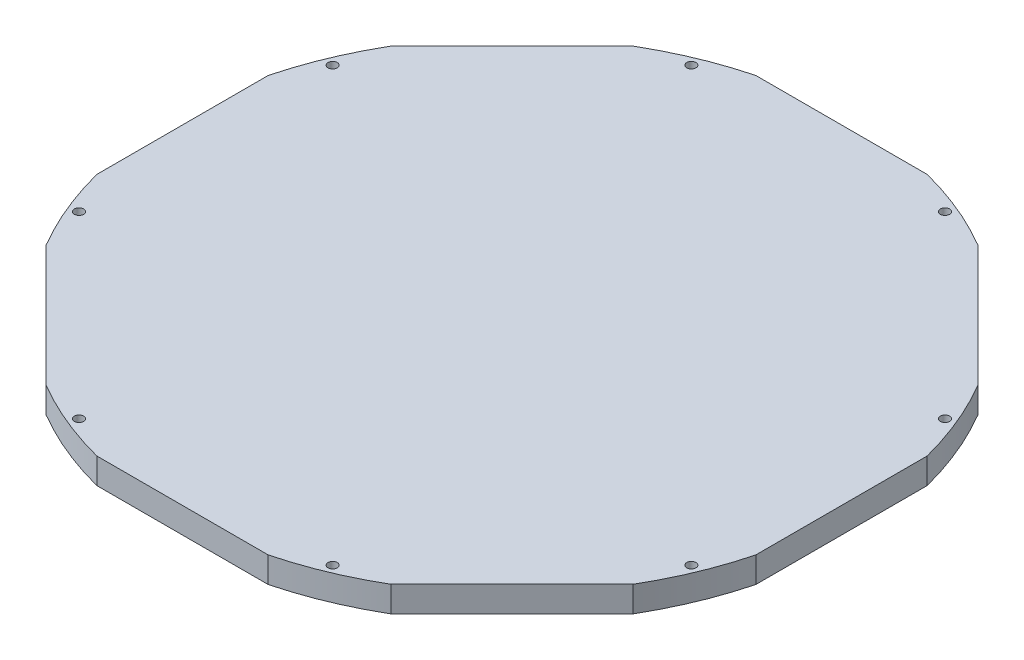
SolidWorks part; units mm, degrees
ref_plane "Front Plane" through (0, 0, 0) normal (0, 0, 1) x (1, 0, 0)
ref_plane "Top Plane" through (0, 0, 0) normal (0, 1, 0) x (1, 0, 0)
ref_plane "Right Plane" through (0, 0, 0) normal (1, 0, 0) x (0, 0, -1)
sketch "Sketch1" plane through (0, 0, 0) normal (0, 1, 0) x (1, 0, 0)
  line L1 (-50.6583, 122.3) -> (-122.3, 50.6583)
  line L2 (-122.3, 50.6583) -> (-122.3, -50.6583)
  line L3 (-122.3, -50.6583) -> (-50.6583, -122.3)
  line L4 (-50.6583, -122.3) -> (50.6583, -122.3)
  line L5 (50.6583, -122.3) -> (122.3, -50.6583)
  line L6 (122.3, -50.6583) -> (122.3, 50.6583)
  line L7 (122.3, 50.6583) -> (50.6583, 122.3)
  line L8 (50.6583, 122.3) -> (-50.6583, 122.3)
  circle A0 centre (0, 0) radius 122.3 construction
  circle A1 centre (0, 0) radius 126.365
  dimension "D2" = 252.73
  dimension "D1" = 244.6
extrude "Boss-Extrude1" add sketch "Sketch1" along normal blind 9.525 contours L4 A1 L5 L6 L7 L8 L1 L2 L3 region at (0, 0, 0)
sketch "Sketch2" plane through (0, 0, 0) normal (0, -1, 0) x (1, 0, 0)
  circle A0 centre (0, 0) radius 115.2525
  circle A1 centre (0, 0) radius 119.0625
  dimension "D1" = 238.125
  dimension "D2" = 230.505
extrude "Cut-Extrude1" cut sketch "Sketch2" against normal blind 2.667
sketch "Sketch3" plane through (0, 9.525, 0) normal (0, 1, 0) x (1, 0, 0)
  line L0 (-63.9978, 108.9605) -> (-31.7934, 122.3) construction
  line L2 (-43.181, 104.2481) -> (-51.6782, 124.7623) construction
  circle A0 centre (0, 0) radius 122.9995
  point P7 (-47.8956, 115.6303)
  point P10 (-47.0699, 113.6367)
  dimension "D1" = 245.999
hole_wizard "#8-32 Tapped Hole1" positions "Sketch4" profile "Sketch5" tap size "#8-32" standard "ANSI Inch" end condition through all
sketch "Sketch4" plane through (0, 9.525, 0) normal (0, 1, 0) x (1, 0, 0)
  point P0 (-47.0699, 113.6367)
sketch "Sketch5" plane through (-47.0699, 9.525, -113.6367) normal (1, 0, 0) x (0, 0, 1)
  line L0 (0, 0) -> (0, 9.525)
  line L1 (0, 9.525) -> (1.7272, 9.525)
  line L2 (1.7272, 9.525) -> (1.7272, 0)
  line L5 (1.7272, 0) -> (0, 0)
  line L11 (0, -6.35) -> (0, 107.95) construction
  dimension "Thru Tap Drill Dia." = 3.4544
  dimension "Thru Tap Drill Depth" = 9.525
cosmetic thread "Hole Thread1" parameters "D2"=4.1656
pattern_circular "CirPattern1" count 8 over 360 about axis through (0, 9.525, 0) along (0, -1, 0) of "#8-32 Tapped Hole1" reverse direction yes
cosmetic thread "Hole Thread2" parameters "D2"=4.1656
cosmetic thread "Hole Thread3" parameters "D2"=4.1656
cosmetic thread "Hole Thread4" parameters "D2"=4.1656
cosmetic thread "Hole Thread5" parameters "D2"=4.1656
cosmetic thread "Hole Thread6" parameters "D2"=4.1656
cosmetic thread "Hole Thread7" parameters "D2"=4.1656
cosmetic thread "Hole Thread8" parameters "D2"=4.1656
